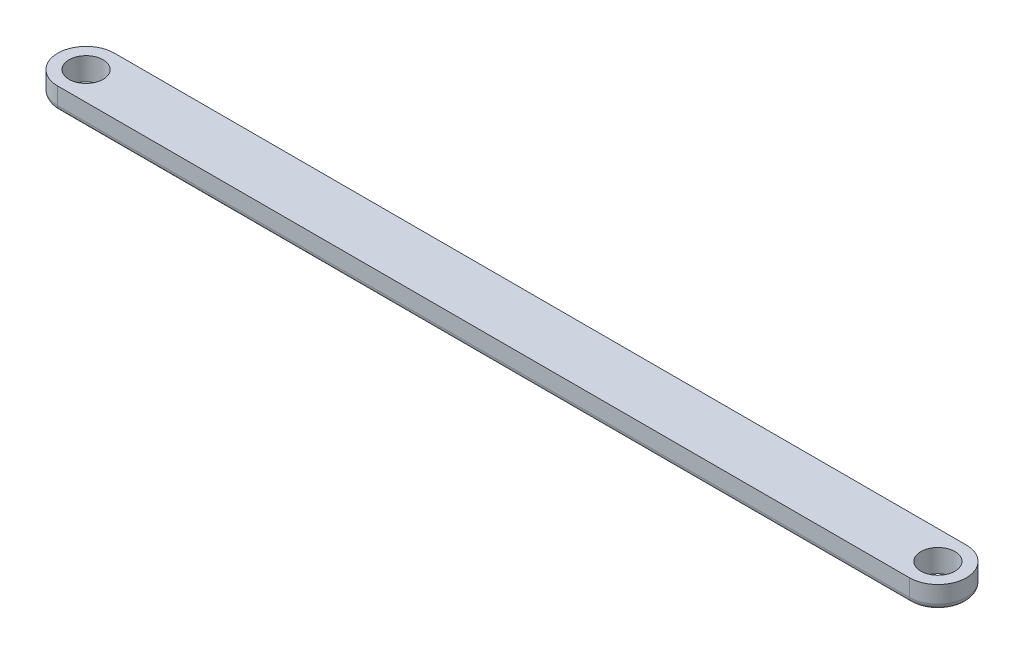
SolidWorks part; units mm, degrees
ref_plane "Front Plane" through (0, 0, 0) normal (0, 0, 1) x (1, 0, 0)
ref_plane "Top Plane" through (0, 0, 0) normal (0, 1, 0) x (1, 0, 0)
ref_plane "Right Plane" through (0, 0, 0) normal (1, 0, 0) x (0, 0, -1)
sketch "Sketch1" plane through (0, 0, 0) normal (0, 1, 0) x (1, 0, 0)
  line L0 (0, 0) -> (150, 0) construction
  line L1 (0, 5) -> (150, 5)
  line L2 (0, -5) -> (150, -5)
  line L3 (0, 5) -> (0, -5) construction
  circle A0 centre (0, 0) radius 3
  circle A1 centre (150, 0) radius 3
  circle A2 centre (0, 0) radius 5
  circle A3 centre (150, 0) radius 5
  dimension "D1" = 6
  dimension "D2" = 6
  dimension "D3" = 10
  dimension "D4" = 10
  dimension "D5" = 150
  dimension "D6" = 10
extrude "Boss-Extrude1" add sketch "Sketch1" along normal blind 4 contours A2 L0 A3 L1 | L0 A2 L2 A3 | A0 A2 | A3 A1 region at (75, 0, 0) region at (3.4355, 0, -3.4355) region at (153.4355, 0, -3.4355)
fillet "Fillet1" radius 1 4 edges at (155, 0, 0) (75, 0, -5) (-5, 0, 0) (75, 0, 5)
